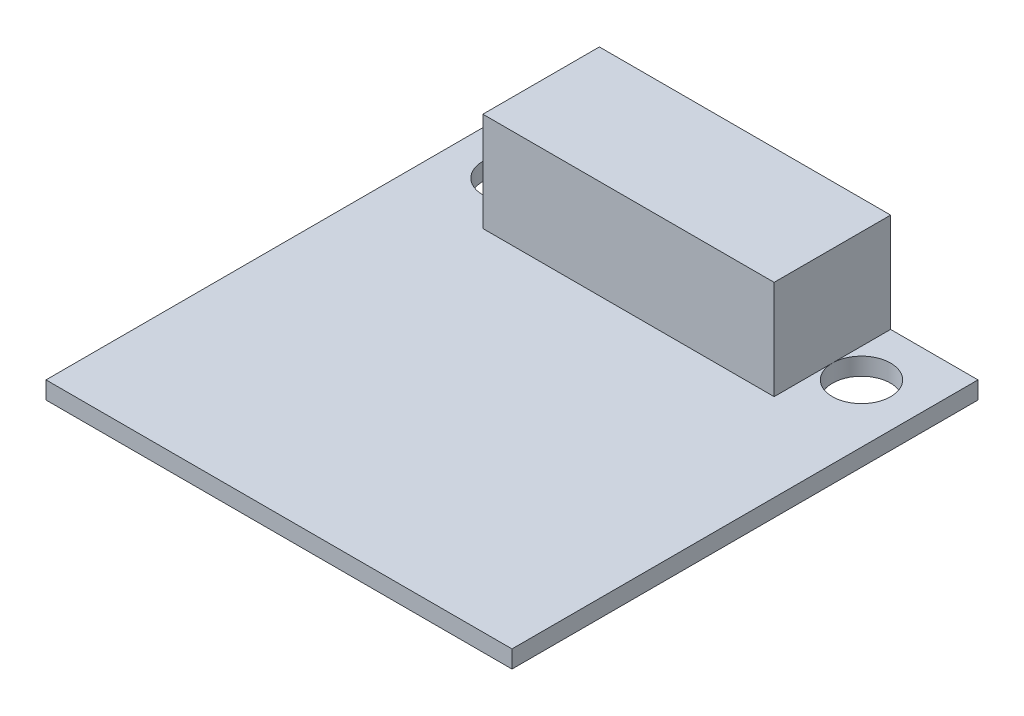
SolidWorks part; units mm, degrees
ref_plane "Front Plane" through (0, 0, 0) normal (0, 0, 1) x (1, 0, 0)
ref_plane "Top Plane" through (0, 0, 0) normal (0, 1, 0) x (1, 0, 0)
ref_plane "Right Plane" through (0, 0, 0) normal (1, 0, 0) x (0, 0, -1)
sketch "Sketch1" plane through (0, 0, 0) normal (0, 1, 0) x (1, 0, 0)
  line L0 (0, 40) -> (0, -40) construction
  line L1 (-40, -40) -> (40, -40)
  line L2 (-40, -40) -> (-40, 40)
  line L3 (-40, 40) -> (40, 40)
  line L4 (40, -40) -> (40, 40)
  line L5 (-40, -40) -> (40, 40) construction
  line L6 (-40, 40) -> (40, -40) construction
  line L7 (0, 0) -> (-30, 0) construction
  line L8 (-30, -40) -> (-30, 30) construction
  line L9 (-25, 30) -> (25, 30) construction
  line L10 (-23, 22) -> (-23, 38)
  line L11 (-25, 20) -> (25, 20)
  line L12 (-25, 20) -> (-25, 40)
  line L13 (-25, 40) -> (25, 40)
  line L14 (25, 20) -> (25, 40)
  line L15 (-25, 20) -> (25, 40) construction
  line L16 (-25, 40) -> (25, 20) construction
  line L18 (23, 22) -> (23, 38)
  line L20 (-23, 38) -> (23, 38) construction
  line L21 (-23, 22) -> (23, 22) construction
  line L22 (30, 30) -> (40, 30) construction
  line L24 (-40, -40) -> (40, -40)
  line L25 (-40, -40) -> (-40, -25)
  line L27 (40, -40) -> (40, -25)
  circle A0 centre (-30, 30) radius 5
  circle A1 centre (30, 30) radius 5
  point P0 (0, 0)
  point P17 (0, 30)
  dimension "D1" = 2
extrude "Boss-Extrude2" add sketch "Sketch1" along normal blind 3 contours L11 L14 L3 L12 | L14 A1 L11 L12 A0 L3 L2 L1 L4 region at (0, 0, 6.6208) region at (0, 0, -30)
extrude "Boss-Extrude3" add sketch "Sketch1<5>" along normal blind 20 contours L11 L14 L3 L12 region at (0, 0, -30)
sketch "Sketch1<5>" plane through (0, 0, 0) normal (0, 1, 0) x (1, 0, 0) same geometry as "Sketch1"
scale "Scale2" scale about centroid uniform scaling yes scale factor 0.1
